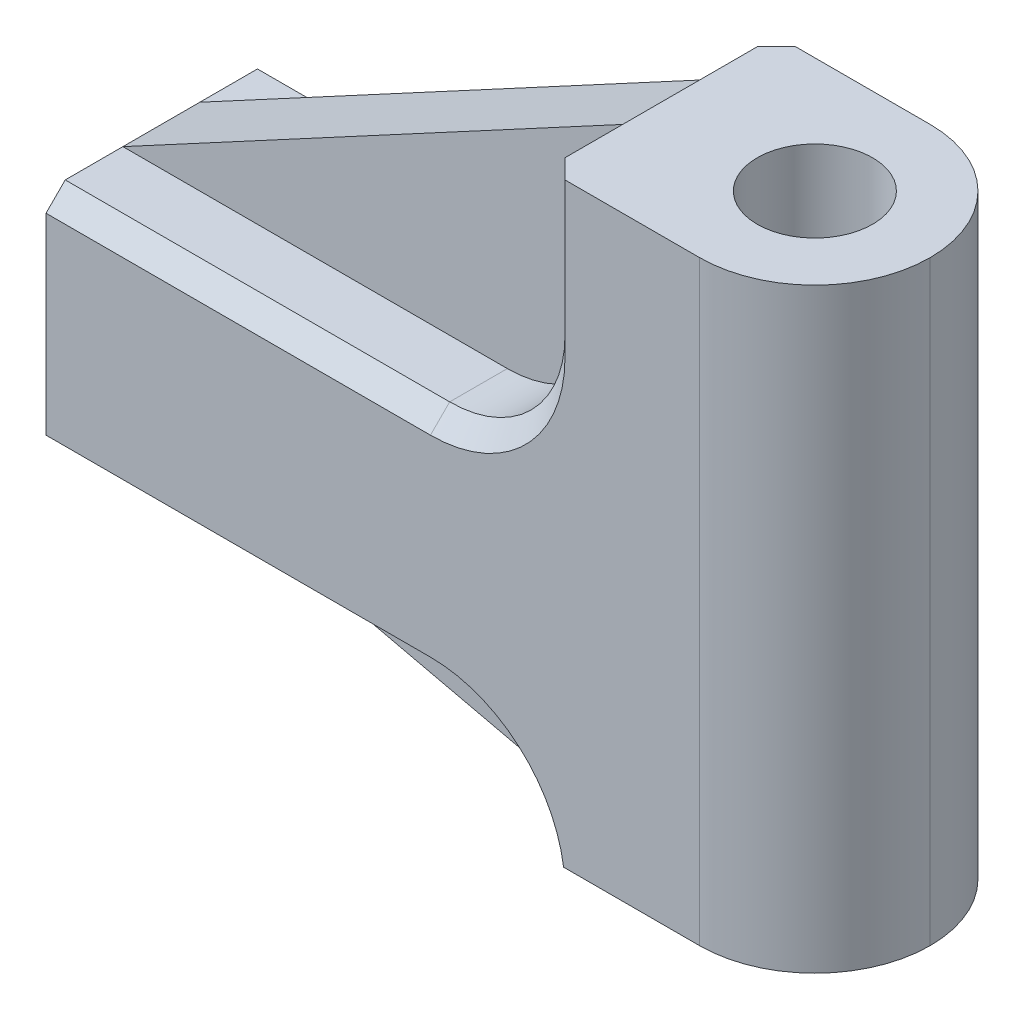
SolidWorks part; units mm, degrees
material "PBT General Purpose"
ref_plane "Front Plane" through (0, 0, 0) normal (0, 0, 1) x (1, 0, 0)
ref_plane "Top Plane" through (0, 0, 0) normal (0, 1, 0) x (1, 0, 0)
ref_plane "Right Plane" through (0, 0, 0) normal (1, 0, 0) x (0, 0, -1)
sketch "Sketch1" plane through (0, 0, 0) normal (0, 1, 0) x (1, 0, 0)
  line L1 (-3.5, 3) -> (3.5, 3)
  line L2 (-3.5, 3) -> (-3.5, -3)
  line L3 (-3.5, -3) -> (3.5, -3)
  line L4 (3.5, 3) -> (3.5, -3)
  line L5 (-3.5, 3) -> (3.5, -3) construction
  line L6 (-3.5, -3) -> (3.5, 3) construction
  point P0 (0, 0)
  dimension "D1" = 7
  dimension "D2" = 6
extrude "Boss-Extrude1" add sketch "Sketch1" along normal blind 16
fillet "Fillet1" radius 3 2 edges at (3.5, 8, 3) (3.5, 8, -3)
sketch "Sketch2" plane through (0, 16, 0) normal (0, 1, 0) x (1, 0, 0)
  circle A0 centre (0.5, 0) radius 1.5
  arc A1 (0.5, -3) -> (3.5, 0) centre (0.5, 0) ccw construction
  dimension "D1" = 3
extrude "Cut-Extrude1" cut sketch "Sketch2" against normal blind 16
sketch "Sketch3" plane through (-3.5, 0, 0) normal (-1, 0, 0) x (0, 0, 1)
  line L0 (-3, 3) -> (3, 3)
  line L1 (-3, 16) -> (-3, 0) construction
  line L2 (3, 16) -> (3, 0) construction
  line L3 (3, 3) -> (3, 9)
  line L4 (3, 9) -> (-3, 9)
  line L5 (-3, 9) -> (-3, 3)
  dimension "D1" = 3
  dimension "D2" = 6
extrude "Boss-Extrude2" add sketch "Sketch3" along normal blind 13
fillet "Fillet2" radius 3 2 edges at (-3.5, 9, 0) (-3.5, 3, 0)
chamfer "Chamfer1" distance 0.5 angle 45 10 edges at (-11.5, 3, 3) (-4.3787, 2.1213, 3) (-11.5, 9, 3) (-4.3787, 9.8787, 3) (-3.5, 14, 3) (-11.5, 9, -3) (-4.3787, 9.8787, -3) (-3.5, 14, -3) (-11.5, 3, -3) (-4.3787, 2.1213, -3)
ref_plane "Plane1" through (0, 0, 0) normal (0, 0, -1) x (-1, 0, 0)
sketch "Sketch6" plane through (0, 0, 0) normal (0, 0, -1) x (-1, 0, 0)
  line L0 (3.5, 16) -> (16.5, 9)
rib "Rib1" sketch "Sketch6" sketch "Sketch6" thickness 2 extrusion direction parallel to sketch draft on no parameters "D1"=2
sketch "Sketch7" plane through (0, 0, 0) normal (0, 0, -1) x (-1, 0, 0)
  line L0 (3.5, 0) -> (16.5, 3)
rib "Rib6" sketch "Sketch7" sketch "Sketch7" thickness 2 extrusion direction parallel to sketch draft on no parameters "D1"=2
sketch "Sketch8" plane through (-16.5, 0, 0) normal (-1, 0, 0) x (0, 0, 1)
  line L0 (0, 8.8) -> (0, -8.8) construction
  line L1 (1, 9) -> (-1, 9) construction
  circle A0 centre (0, 6) radius 1.25
  dimension "D2" = 2.5
  dimension "D1" = 3
extrude "Cut-Extrude4" cut sketch "Sketch8" against normal blind 15
cosmetic thread "Cosmetic Thread1" parameters "D2"=3
sketch "Sketch10" plane through (0, 0, 0) normal (1, 0, 0) x (0, 0, -1)
  line L0 (3, 16) -> (3, 0) construction
  line L1 (-3, 0) -> (3, 0)
  line L2 (-3, 0) -> (-3, 0.5)
  line L3 (-3, 0.5) -> (3, 0.5)
  line L4 (3, 0) -> (3, 0.5)
  dimension "D1" = 0.5
extrude "Cut-Extrude6" cut sketch "Sketch10" against normal through all both and the other way through all
